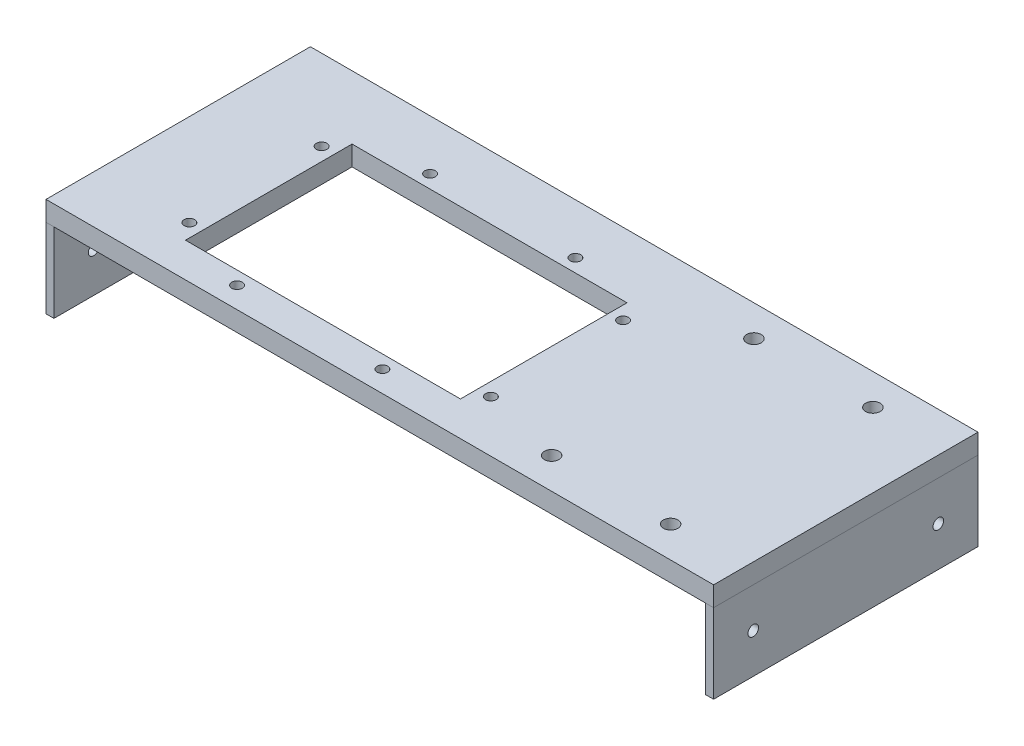
SolidWorks part; units mm, degrees
material "Plain Carbon Steel"
ref_plane "Front Plane" through (0, 0, 0) normal (0, 0, 1) x (1, 0, 0)
ref_plane "Top Plane" through (0, 0, 0) normal (0, 1, 0) x (1, 0, 0)
ref_plane "Right Plane" through (0, 0, 0) normal (1, 0, 0) x (0, 0, -1)
sketch "Sketch1" plane through (0, 0, 0) normal (0, 1, 0) x (1, 0, 0)
  line L0 (0, 0) -> (-252.5, 0) construction
  line L1 (0, 0) -> (0, 100) construction
  line L8 (252.5, 100) -> (-252.5, 100)
  line L9 (-252.5, 100) -> (-252.5, -100)
  line L10 (-252.5, -100) -> (252.5, -100)
  line L11 (252.5, -100) -> (252.5, 100)
  circle A4 centre (227.5, -75) radius 5 construction
  circle A5 centre (227.5, 75) radius 5 construction
  circle A6 centre (-227.5, -75) radius 5 construction
  circle A7 centre (-227.5, 75) radius 5 construction
  circle A16 centre (106.5, -76.5) radius 5.5 construction
  circle A17 centre (196.5, -76.5) radius 5.5 construction
  circle A18 centre (196.5, 76.5) radius 5.5 construction
  circle A19 centre (106.5, 76.5) radius 5.5 construction
  circle A20 centre (106.5, -76.5) radius 5.5
  circle A21 centre (196.5, -76.5) radius 5.5
  circle A22 centre (196.5, 76.5) radius 5.5
  circle A23 centre (106.5, 76.5) radius 5.5
  circle A24 centre (45, -61) radius 4 construction
  circle A25 centre (-14, -84) radius 4 construction
  circle A26 centre (-124, -84) radius 4 construction
  circle A27 centre (-183, -61) radius 4 construction
  circle A28 centre (-183, 39) radius 4 construction
  circle A29 centre (-124, 62) radius 4 construction
  circle A30 centre (45, 39) radius 4 construction
  circle A31 centre (-14, 62) radius 4 construction
  circle A32 centre (45, -61) radius 4
  circle A33 centre (-14, -84) radius 4
  circle A34 centre (-124, -84) radius 4
  circle A35 centre (-183, -61) radius 4
  circle A36 centre (-183, 39) radius 4
  circle A37 centre (-124, 62) radius 4
  circle A38 centre (45, 39) radius 4
  circle A39 centre (-14, 62) radius 4
  dimension "D4" = 25
  dimension "D5" = 10
  dimension "D1" = 505
  dimension "D2" = 200
  dimension "D3" = 25
extrude "Boss-Extrude1" add sketch "Sketch1" against normal blind 15
sketch "Sketch2" plane through (0, -15, 0) normal (0, -1, 0) x (1, 0, 0)
  line L0 (35, -102) -> (35, 94) construction
  line L1 (-173, 74) -> (35, 74)
  line L2 (-173, 74) -> (-173, -52)
  line L3 (-173, -52) -> (35, -52)
  line L4 (35, 74) -> (35, -52)
  line L5 (35, 74) -> (-173, 74) construction
  line L6 (-173, -52) -> (35, -52) construction
  line L7 (-173, 94) -> (-173, -72) construction
extrude "Shredder Opening" cut sketch "Sketch2" against normal through all
sketch "Sketch3" plane through (0, 0, 0) normal (0, 1, 0) x (1, 0, 0)
  line L0 (252.5, 100) -> (-252.5, 100) construction
  line L1 (200, 100) -> (30, 100)
  line L2 (200, 100) -> (200, 176.5)
  line L3 (200, 176.5) -> (30, 176.5)
  line L4 (30, 100) -> (30, 176.5)
  line L8 (115, 176.5) -> (115, 267.7218) construction
  circle A1 centre (175, 151.5) radius 5
  circle A2 centre (55, 151.5) radius 5
extrude "Legs add on" [suppressed] add sketch "Sketch3" against normal through all
sketch "Sketch4" plane through (0, 0, 100) normal (0, 0, 1) x (1, 0, 0)
  line L0 (0, -15) -> (0, -97.7912) construction
  line L1 (-252.5, -15) -> (-246.5, -15)
  line L2 (-252.5, -15) -> (-252.5, -75)
  line L3 (-252.5, -75) -> (-246.5, -75)
  line L4 (-246.5, -15) -> (-246.5, -75)
  line L5 (-252.5, -15) -> (252.5, -15) construction
  line L6 (246.5, -15) -> (246.5, -75)
  line L7 (252.5, -75) -> (246.5, -75)
  line L8 (252.5, -15) -> (252.5, -75)
  line L9 (252.5, -15) -> (246.5, -15)
  point P9 (0, 0)
  dimension "D1" = 60
  dimension "D2" = 6
extrude "Boss-Extrude2" add sketch "Sketch4" against normal through all separate body
sketch "Sketch5" plane through (-252.5, 0, 0) normal (-1, 0, 0) x (0, 0, 1)
  line L0 (0, -75) -> (0, -118.3722) construction
  line L1 (-100, -75) -> (100, -75) construction
  line L2 (100, -15) -> (100, -75) construction
  circle A0 centre (70, -45) radius 4
  circle A1 centre (-70, -45) radius 4
  point P11 (100, -45)
  dimension "D1" = 8
  dimension "D2" = 26
extrude "Cut-Extrude1" cut sketch "Sketch5" against normal through all
